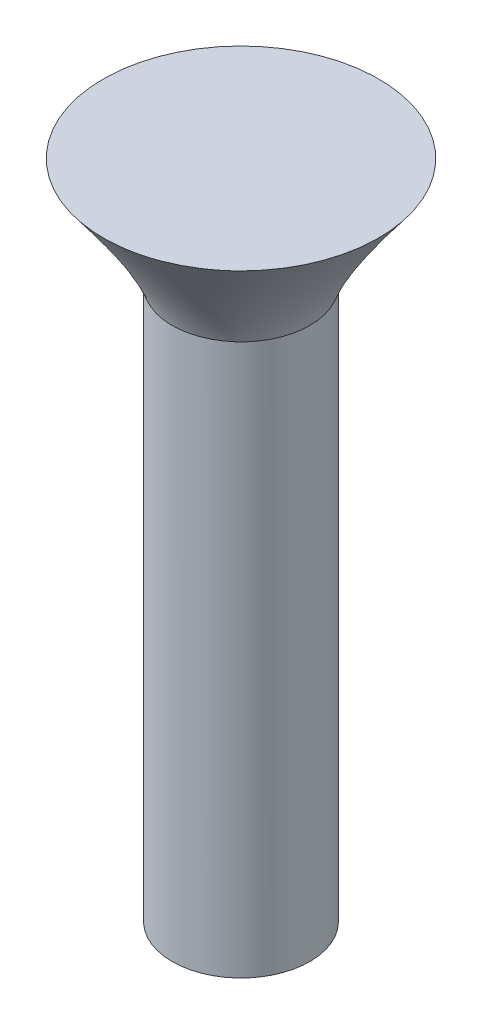
SolidWorks part; units mm, degrees
ref_plane "Front Plane" through (0, 0, 0) normal (0, 0, 1) x (1, 0, 0)
ref_plane "Top Plane" through (0, 0, 0) normal (0, 1, 0) x (1, 0, 0)
ref_plane "Right Plane" through (0, 0, 0) normal (1, 0, 0) x (0, 0, -1)
sketch "Sketch1" plane through (0, 0, 0) normal (0, 1, 0) x (1, 0, 0)
  circle A0 centre (0, 0) radius 2.5
  dimension "D1" = 5
extrude "Boss-Extrude1" add sketch "Sketch1" along normal blind 20
ref_plane "Plane1" through (0, 24, 0) normal (0, 1, 0) x (1, 0, 0)
sketch "Sketch2" plane through (0, 24, 0) normal (0, 1, 0) x (1, 0, 0)
  circle A0 centre (0, 0) radius 5
  dimension "D1" = 10
sketch "Sketch3" plane through (0, 20, 0) normal (0, 1, 0) x (1, 0, 0)
  circle A1 centre (0, 0) radius 2.5
  circle A2 centre (0, 0) radius 2.5
  dimension "D1" = 0
loft "Loft1" add profiles "Sketch3", "Sketch2" connector at (-2.2785, 20, -1.0288) connector at (-2.2531, 24, -4.4636)
